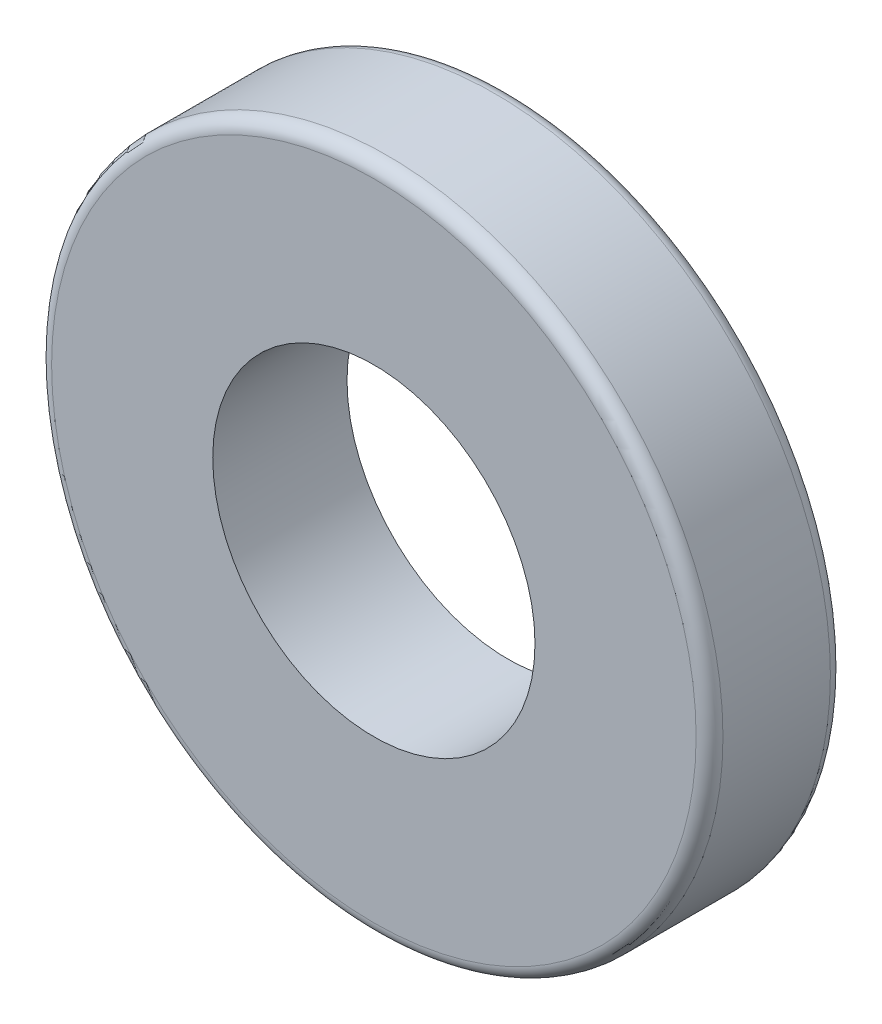
SolidWorks part; units mm, degrees
ref_plane "Front Plane" through (0, 0, 0) normal (0, 0, 1) x (1, 0, 0)
ref_plane "Top Plane" through (0, 0, 0) normal (0, 1, 0) x (1, 0, 0)
ref_plane "Right Plane" through (0, 0, 0) normal (1, 0, 0) x (0, 0, -1)
sketch "Sketch1" plane through (0, 0, 0) normal (0, 0, 1) x (1, 0, 0)
  circle A0 centre (0, 0) radius 6.35
  dimension "D1" = 12.7
extrude "Boss-Extrude1" add sketch "Sketch1" along normal blind 2.54
sketch "Sketch2" plane through (0, 0, 2.54) normal (0, 0, 1) x (1, 0, 0)
  circle A0 centre (0, 0) radius 3.048
  dimension "D1" = 6.096
extrude "Cut-Extrude1" cut sketch "Sketch2" against normal through all
ref_axis "Axis1" through (0, 0, 0) along (0, 0, 1)
fillet "Fillet1" radius 0.254 2 edges at (6.35, 0, 0) (6.35, 0, 2.54)
